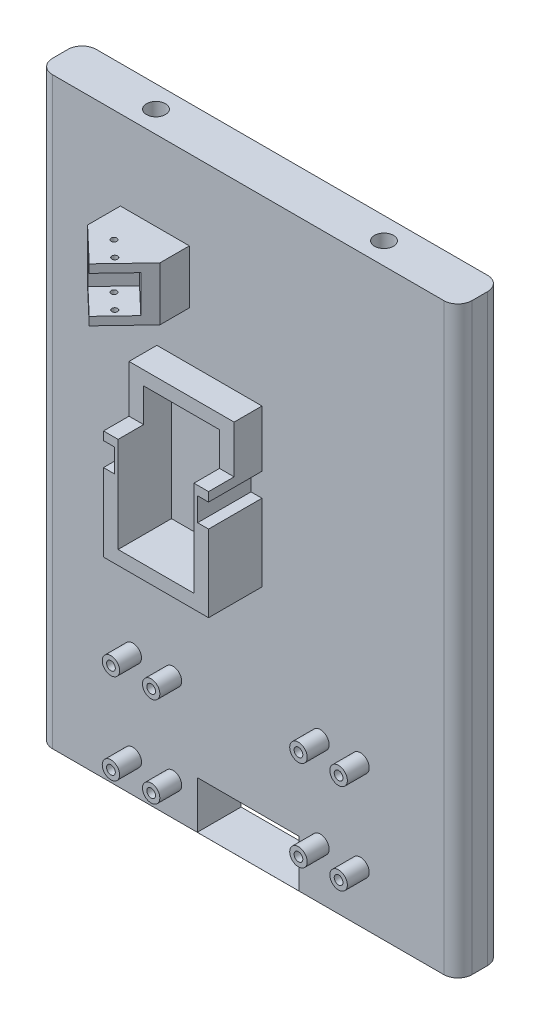
SolidWorks part; units mm, degrees
ref_plane "Front Plane" through (0, 0, 0) normal (0, 0, 1) x (1, 0, 0)
ref_plane "Top Plane" through (0, 0, 0) normal (0, 1, 0) x (1, 0, 0)
ref_plane "Right Plane" through (0, 0, 0) normal (1, 0, 0) x (0, 0, -1)
sketch "Sketch1" plane through (0, 0, 0) normal (0, 0, 1) x (1, 0, 0)
  line L1 (0, 0) -> (101.6, 0)
  line L2 (0, 0) -> (0, 203.2)
  line L3 (0, 203.2) -> (101.6, 203.2)
  line L4 (101.6, 0) -> (101.6, 203.2)
  dimension "D1" = 101.6
  dimension "D2" = 203.2
extrude "Boss-Extrude1" add sketch "Sketch1" along normal mid plane 15.24
fillet "Fillet1" radius 6.35 1 edges at (101.6, 101.6, 7.62)
fillet "Fillet2" radius 6.35 1 edges at (101.6, 101.6, -7.62)
fillet "Fillet3" radius 6.35 1 edges at (0, 101.6, -7.62)
fillet "Fillet4" radius 6.35 1 edges at (0, 101.6, 7.62)
sketch "Sketch4" plane through (0, 0, 7.62) normal (0, 0, 1) x (1, 0, 0)
  line L0 (6.35, 203.2) -> (6.35, 0) construction
  line L1 (6.35, 175.418) -> (30.35, 175.418)
  line L2 (6.35, 175.418) -> (6.35, 156.718)
  line L3 (6.35, 156.718) -> (30.35, 156.718)
  line L4 (30.35, 175.418) -> (30.35, 156.718)
  line L5 (95.25, 0) -> (95.25, 203.2) construction
  line L6 (95.25, 58.42) -> (71.7296, 58.42)
  line L7 (95.25, 58.42) -> (95.25, 7.62)
  line L8 (95.25, 7.62) -> (71.7296, 7.62)
  line L9 (71.7296, 58.42) -> (71.7296, 7.62)
  line L10 (6.35, 0) -> (95.25, 0) construction
  line L11 (6.35, 7.62) -> (29.083, 7.62)
  line L12 (6.35, 7.62) -> (6.35, 47.1424)
  line L13 (6.35, 47.1424) -> (29.083, 47.1424)
  line L14 (29.083, 7.62) -> (29.083, 47.1424)
  line L15 (19.05, 139.7762) -> (55.626, 139.7762)
  line L16 (19.05, 139.7762) -> (19.05, 85.2424)
  line L17 (19.05, 85.2424) -> (55.626, 85.2424)
  line L18 (55.626, 139.7762) -> (55.626, 85.2424)
  line L25 (95.25, 203.2) -> (6.35, 203.2) construction
  line L26 (33.1089, 0) -> (68.4911, 0)
  line L27 (33.1089, 0) -> (33.1089, 16.5016)
  line L28 (24.13, 134.9502) -> (50.546, 134.9502)
  line L29 (24.13, 134.9502) -> (24.13, 90.0684)
  line L30 (24.13, 90.0684) -> (50.546, 90.0684)
  line L31 (50.546, 134.9502) -> (50.546, 90.0684)
  line L32 (33.1089, 16.5016) -> (68.4911, 16.5016)
  line L33 (68.4911, 0) -> (68.4911, 16.5016)
  point P24 (50.8254, 6.35)
  point P27 (50.8, 16.5016)
  point P36 (50.8, 203.2)
  dimension "D1" = 24
  dimension "D2" = 18.7
  dimension "D3" = 50.8
  dimension "D4" = 23.5204
  dimension "D5" = 22.733
  dimension "D6" = 39.5224
  dimension "D7" = 36.576
  dimension "D8" = 54.5338
  dimension "D9" = 7.62
  dimension "D10" = 35.3821
  dimension "D11" = 12.7
  dimension "D12" = 38.1
  dimension "D13" = 16.5016
  dimension "D14" = 44.4754
  dimension "D15" = 196.85
  dimension "D16" = 4.826
  dimension "D17" = 4.826
  dimension "D18" = 5.08
  dimension "D19" = 5.08
  dimension "D20" = 156.718
sketch "Sketch5" plane through (0, 0, 7.62) normal (0, 0, 1) x (1, 0, 0)
  line L1 (19.05, 139.7762) -> (55.626, 139.7762)
  line L2 (19.05, 139.7762) -> (19.05, 85.2424)
  line L3 (19.05, 85.2424) -> (55.626, 85.2424)
  line L4 (55.626, 139.7762) -> (55.626, 85.2424)
  line L5 (24.13, 134.9502) -> (50.546, 134.9502)
  line L6 (24.13, 134.9502) -> (24.13, 90.0684)
  line L7 (24.13, 90.0684) -> (50.546, 90.0684)
  line L8 (50.546, 134.9502) -> (50.546, 90.0684)
extrude "Boss-Extrude2" add sketch "Sketch5" along normal blind 18.5928 contours L2 L1 L4 L3 | L6 L5 L8 L7
sketch "Sketch7" plane through (0, 0, 7.62) normal (0, 0, 1) x (1, 0, 0)
  line L0 (6.35, 203.2) -> (6.35, 0) construction
  line L1 (6.35, 175.418) -> (30.35, 175.418)
  line L2 (6.35, 175.418) -> (6.35, 156.718)
  line L3 (6.35, 156.718) -> (30.35, 156.718)
  line L4 (30.35, 175.418) -> (30.35, 156.718)
  line L5 (6.35, 0) -> (95.25, 0) construction
  dimension "D1" = 18.7
  dimension "D2" = 24
  dimension "D3" = 156.718
extrude "Boss-Extrude3" add sketch "Sketch7" along normal blind 22.86
sketch "Sketch9" plane through (0, 0, 7.62) normal (0, 0, 1) x (1, 0, 0)
  line L0 (55.626, 139.7762) -> (55.626, 85.2424) construction
  line L1 (55.626, 120.1025) -> (51.816, 120.1025)
  line L2 (55.626, 120.1025) -> (55.626, 111.9745)
  line L3 (55.626, 111.9745) -> (51.816, 111.9745)
  line L4 (51.816, 120.1025) -> (51.816, 111.9745)
  line L5 (19.05, 139.7762) -> (19.05, 85.2424) construction
  line L6 (19.05, 120.3474) -> (22.86, 120.3474)
  line L7 (19.05, 120.3474) -> (19.05, 112.2194)
  line L8 (19.05, 112.2194) -> (22.86, 112.2194)
  line L9 (22.86, 120.3474) -> (22.86, 112.2194)
  line L10 (6.35, 156.718) -> (6.35, 0) construction
  line L11 (6.35, 156.718) -> (30.35, 156.718) construction
  dimension "D1" = 3.81
  dimension "D2" = 8.128
  dimension "D3" = 36.3706
  dimension "D4" = 36.6155
extrude "Cut-Extrude3" cut sketch "Sketch9" against normal through all both and the other way through all
ref_plane "Plane1" through (55.626, 0, 0) normal (1, 0, 0) x (0, 0, -1)
sketch "Sketch23" plane through (55.626, 0, 0) normal (1, 0, 0) x (0, 0, -1)
  line L1 (-26.2128, 139.7762) -> (-17.3228, 139.7762)
  line L2 (-26.2128, 139.7762) -> (-26.2128, 123.2662)
  line L3 (-26.2128, 123.2662) -> (-17.3228, 123.2662)
  line L4 (-17.3228, 139.7762) -> (-17.3228, 123.2662)
  dimension "D1" = 8.89
  dimension "D2" = 16.51
extrude "Cut-Extrude9" cut sketch "Sketch23" against normal through all
ref_plane "Plane2" through (0, 175.418, 0) normal (0, 1, 0) x (1, 0, 0)
sketch "Sketch12" plane through (0, 175.418, 0) normal (0, 1, 0) x (1, 0, 0)
  line L0 (6.35, -19.05) -> (18.35, -30.48)
  line L1 (6.35, -30.48) -> (6.35, -7.62) construction
  line L2 (30.35, -30.48) -> (6.35, -30.48) construction
  line L3 (18.35, -30.48) -> (30.35, -17.8816)
  line L4 (30.35, -30.48) -> (30.35, -7.62) construction
  line L5 (6.35, -19.05) -> (6.35, -30.48)
  line L6 (6.35, -30.48) -> (30.35, -30.48)
  line L7 (30.35, -30.48) -> (30.35, -17.8816)
extrude "Cut-Extrude5" cut sketch "Sketch12" against normal blind 20.574 contours L5 L6 L0 | L6 L7 L3 region at (26.35, 175.418, 26.2805) region at (10.35, 175.418, 26.67)
ref_plane "Plane3" through (0, 166.068, 0) normal (0, -1, 0) x (-1, 0, 0)
sketch "Sketch13" plane through (0, 166.068, 0) normal (0, -1, 0) x (-1, 0, 0)
  line L10 (-18.35, -30.48) -> (-27.1092, -21.284)
  line L11 (-18.35, -30.48) -> (-30.35, -17.8816) construction
  line L13 (-27.1092, -21.284) -> (-17.9132, -12.5248)
  line L14 (-17.9132, -12.5248) -> (-9.154, -21.7208)
  line L15 (-6.35, -19.05) -> (-18.35, -30.48) construction
  line L16 (-9.154, -21.7208) -> (-18.35, -30.48)
  dimension "D1" = 12.7
  dimension "D2" = 12.7
extrude "Cut-Extrude6" cut sketch "Sketch13" against normal mid plane 12.954
sketch "Sketch14" plane through (0, 0, 7.62) normal (0, 0, 1) x (1, 0, 0)
  line L0 (6.35, 7.62) -> (6.35, 47.1424) construction
  circle A0 centre (10.668, 42.83) radius 1.524
  circle A1 centre (24.668, 42.83) radius 1.524
  circle A2 centre (10.668, 11.43) radius 1.524
  circle A3 centre (24.668, 11.43) radius 1.524
  circle A4 centre (10.668, 42.83) radius 3.0226
  circle A5 centre (24.668, 42.83) radius 3.0226
  circle A6 centre (24.668, 11.43) radius 3.0226
  circle A7 centre (10.668, 11.43) radius 3.0226
  dimension "D1" = 3.048
  dimension "D2" = 14
  dimension "D6" = 6.0452
  dimension "D3" = 31.4
  dimension "D4" = 4.318
  dimension "D5" = 3.81
extrude "Boss-Extrude4" add sketch "Sketch14" along normal blind 7.62
sketch "Sketch16" plane through (0, 0, 7.62) normal (0, 0, 1) x (1, 0, 0)
  line L0 (55.626, 139.7762) -> (55.626, 120.1025) construction
  line L1 (19.05, 139.7762) -> (55.626, 139.7762) construction
  circle A0 centre (75.946, 17.8562) radius 1.524
  circle A1 centre (89.916, 17.8562) radius 1.524
  circle A2 centre (89.916, 49.3522) radius 1.524
  circle A3 centre (75.946, 49.3522) radius 1.524
  circle A4 centre (75.946, 49.3522) radius 3.048
  circle A5 centre (89.916, 49.3522) radius 3.048
  circle A6 centre (75.946, 17.8562) radius 3.048
  circle A7 centre (89.916, 17.8562) radius 3.048
  dimension "D1" = 3.048
  dimension "D6" = 121.92
  dimension "D2" = 6.096
  dimension "D3" = 20.32
  dimension "D4" = 13.97
  dimension "D5" = 31.496
extrude "Boss-Extrude5" add sketch "Sketch16" along normal blind 7.62
sketch "Sketch18" plane through (0, 175.418, 0) normal (0, 1, 0) x (1, 0, 0)
  line L0 (18.35, -30.48) -> (27.1092, -21.284)
  line L1 (18.35, -30.48) -> (30.35, -17.8816) construction
  line L2 (27.1092, -21.284) -> (17.9132, -12.5248)
  line L3 (17.9132, -12.5248) -> (9.154, -21.7208)
  line L4 (13.1346, -16.7428) -> (22.3306, -25.502) construction
  line L5 (9.154, -21.7208) -> (18.35, -30.48)
  line L6 (6.35, -19.05) -> (18.35, -30.48) construction
  circle A0 centre (15.3728, -18.8746) radius 1
  circle A1 centre (20.8904, -24.1302) radius 1
  dimension "D3" = 2
  dimension "D1" = 12.7
  dimension "D2" = 12.7
  dimension "D4" = 7.62
  dimension "D5" = 2.54
  dimension "D6" = 6.35
extrude "Cut-Extrude7" cut sketch "Sketch18" against normal blind 18.7 contours L4 A1 | A1 L4 | A0 region at (21.1831, 175.418, 23.8228) region at (20.5977, 175.418, 24.4375)
sketch "Sketch22" plane through (0, 0, 7.62) normal (0, 0, 1) x (1, 0, 0)
  line L1 (33.1089, 0) -> (68.4911, 0)
  line L2 (33.1089, 0) -> (33.1089, 16.5016)
  line L3 (33.1089, 16.5016) -> (68.4911, 16.5016)
  line L4 (68.4911, 0) -> (68.4911, 16.5016)
extrude "Cut-Extrude8" cut sketch "Sketch22" against normal through all
sketch "Sketch25" plane through (0, 16.5016, 0) normal (0, -1, 0) x (-1, 0, 0)
  line L0 (-33.1089, 0) -> (-68.4911, 0) construction
  line L5 (-33.1089, 7.62) -> (-33.1089, -7.62) construction
  line L6 (-68.4911, 7.62) -> (-68.4911, -7.62) construction
  line L7 (-33.1089, -7.62) -> (-68.4911, -7.62) construction
  line L8 (22.225, -7.62) -> (-123.825, -7.62)
  line L9 (22.225, -7.62) -> (22.225, 7.62)
  line L10 (22.225, 7.62) -> (-123.825, 7.62)
  line L11 (-123.825, -7.62) -> (-123.825, 7.62)
  line L12 (-68.4911, 7.62) -> (-33.1089, 7.62) construction
  point P14 (-50.8, 0)
  dimension "D1" = 146.05
  dimension "D2" = 73.025
extrude "Boss-Extrude6" add sketch "Sketch25" against normal up to surface (186.6984 mm away) from offset 16.51 up to face at (50.8, 203.2, 0)
sketch "Sketch2" plane through (0, 203.2, 0) normal (0, 1, 0) x (1, 0, 0)
  circle A0 centre (11.1125, 0) radius 3.302
  circle A1 centre (90.4875, 0) radius 3.302
  dimension "D1" = 79.375
  dimension "D2" = 6.604
  dimension "D3" = 11.1125
extrude "Cut-Extrude1" cut sketch "Sketch2" against normal through all
fillet "Fillet5" radius 4.92 4 edges at (123.825, 101.5958, -7.62) (123.825, 101.5958, 7.62) (-22.225, 101.5958, -7.62) (-22.225, 101.5958, 7.62)
sketch "Sketch26" plane through (0, 0, 7.62) normal (0, 0, 1) x (1, 0, 0)
  line L1 (33.1089, 16.5016) -> (68.4911, 16.5016)
  line L2 (33.1089, 16.5016) -> (33.1089, 0)
  line L3 (33.1089, 0) -> (68.4911, 0)
  line L4 (68.4911, 16.5016) -> (68.4911, 0)
extrude "Cut-Extrude10" cut sketch "Sketch26" against normal through all
